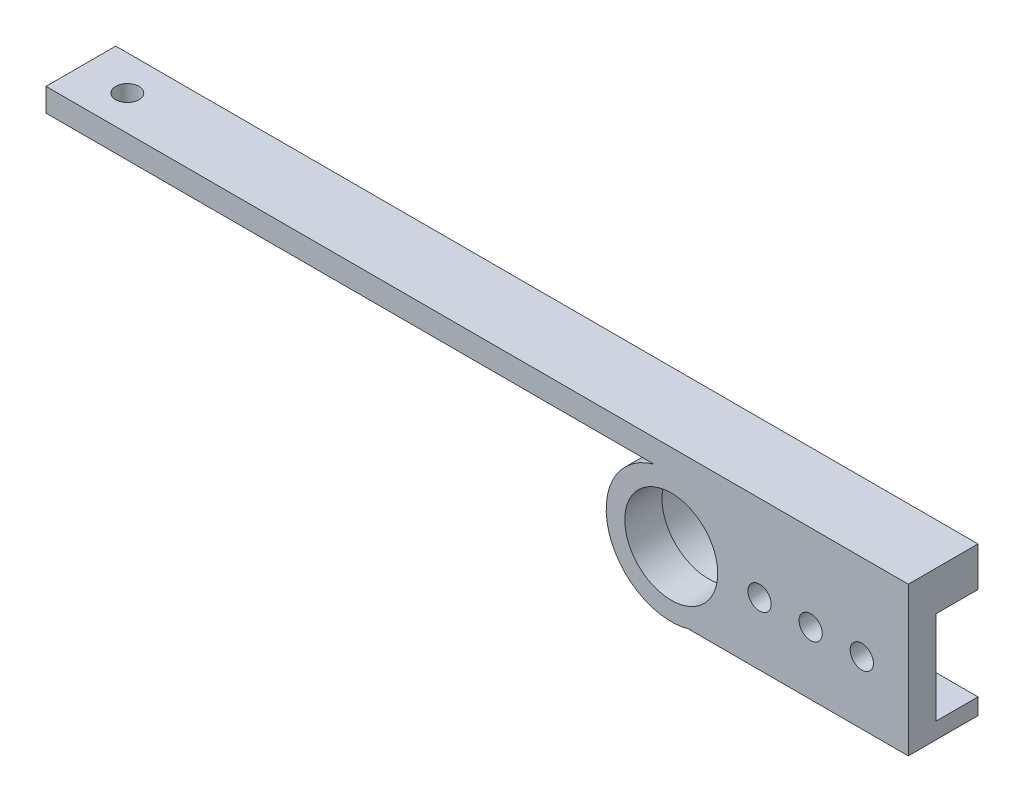
SolidWorks part; units mm, degrees
ref_plane "前视基准面" through (0, 0, 0) normal (0, 0, 1) x (1, 0, 0)
ref_plane "上视基准面" through (0, 0, 0) normal (0, 1, 0) x (1, 0, 0)
ref_plane "右视基准面" through (0, 0, 0) normal (1, 0, 0) x (0, 0, -1)
sketch "草图1" plane through (0, 0, 0) normal (0, 0, 1) x (1, 0, 0)
  line L1 (20, -10) -> (-20, -10)
  line L2 (20, -10) -> (20, 10)
  line L3 (20, 10) -> (-20, 10)
  line L4 (-20, -10) -> (-20, 10)
  line L5 (20, -10) -> (-20, 10) construction
  line L6 (20, 10) -> (-20, -10) construction
  point P0 (0, 0)
  dimension "D1" = 40
  dimension "D2" = 20
extrude "凸台-拉伸1" add sketch "草图1" along normal blind 6
sketch "草图2" plane through (0, 0, 6) normal (0, 0, 1) x (1, 0, 0)
  line L0 (20, -10) -> (20, 10) construction
  circle A0 centre (10, 0) radius 2.5
  circle A1 centre (-1, 0) radius 2.5
  circle A2 centre (-12, 0) radius 2.5
  dimension "D1" = 10
  dimension "D2" = 5
  dimension "D3" = 3
extrude "切除-拉伸1" cut sketch "草图2" against normal through all
sketch "草图3" plane through (0, 0, 6) normal (0, 0, 1) x (1, 0, 0)
  line L0 (20, 13.5) -> (20, 10)
  line L1 (20, -13.5) -> (-26.894, -13.5)
  line L3 (20, 13.5) -> (-26.894, 13.5)
  line L4 (-20, 10) -> (-20, -10)
  line L5 (-20, -10) -> (20, -10)
  line L6 (20, -10) -> (20, 10)
  line L7 (20, 10) -> (-20, 10)
  line L8 (-20, 10) -> (-20, -10)
  line L9 (-20, -10) -> (20, -10)
  line L10 (20, -10) -> (20, 10)
  line L11 (20, 10) -> (-20, 10)
  line L12 (-26.894, -13.5) -> (-26.894, 13.5)
  line L13 (20, -10.0394) -> (-26.894, 13.5) construction
  line L14 (20, 10.0394) -> (-26.894, -13.5) construction
  line L15 (20, -10) -> (20, -13.5)
  circle A0 centre (-31, 0) radius 11
  circle A1 centre (-31, 0) radius 14
  point P2 (0, 0)
  line M10 (-20, 10) -> (-20, -10)
  line M11 (-20, -10) -> (20, -10)
  line M13 (20, 10) -> (-20, 10)
  dimension "D3" = 22
  dimension "D4" = 28
  dimension "D2" = 3.5
  dimension "D1" = 0
extrude "凸台-拉伸2" add sketch "草图3" against normal blind 15 contours L3 A1 L1 L12 A0 | A1 L1 L15 M11 M10 | L1 A1 L8 A0 L12 | L8 A1 L3 L12 A0 | L8 A1 | A1 L0 L3 M10 M13 region at (-1.9449, 11.7771, 6) region at (-1.9449, -11.7771, 6) region at (-23.0173, 9.0328, 6) region at (-27.2274, 11.7946, 6) region at (-18.7882, 0, 6) region at (-23.0173, -9.0328, 6)
sketch "草图5" plane through (0, 0, 6) normal (0, 0, 1) x (1, 0, 0)
  circle A0 centre (-31, 0) radius 10
  circle A1 centre (-31, 0) radius 11 construction
  circle A2 centre (-31, 0) radius 11
  dimension "D1" = 20
extrude "凸台-拉伸3" add sketch "草图5" against normal blind 8
sketch "草图6" plane through (0, 0, 6) normal (0, 0, 1) x (1, 0, 0)
  circle A0 centre (-31, 0) radius 8.5
  circle A1 centre (-31, 0) radius 10 construction
  circle A2 centre (-31, 0) radius 10
  dimension "D1" = 17
sketch "草图7" plane through (0, 13.5, 0) normal (0, 1, 0) x (1, 0, 0)
  circle A0 centre (-17.1666, 1.953) radius 2.6594
sketch "草图8" plane through (20, 0, 0) normal (1, 0, 0) x (0, 0, -1)
  line L1 (-6, 13.5) -> (9, 13.5)
  line L2 (-6, 13.5) -> (-6, 18.5)
  line L3 (-6, 18.5) -> (9, 18.5)
  line L4 (9, 13.5) -> (9, 18.5)
  dimension "D1" = 5
extrude "凸台-拉伸4" add sketch "草图8" against normal blind 500
sketch "草图9" plane through (0, 0, -9) normal (0, 0, -1) x (-1, 0, 0)
  line L1 (24.4567, 15.8334) -> (28.494, 15.8334)
  line L2 (24.4567, 15.8334) -> (24.4567, 12.469)
  line L3 (24.4567, 12.469) -> (28.494, 12.469)
  line L4 (28.494, 15.8334) -> (28.494, 12.469)
extrude "凸台-拉伸5" add sketch "草图9" against normal through all
sketch "草图10" plane through (0, 18.5, 0) normal (0, 1, 0) x (1, 0, 0)
  line L0 (-165.5205, -66.7347) -> (-165.5205, 9)
  line L1 (-165.5205, -66.7347) -> (-49.8553, -66.7347) construction
  line L2 (-165.5205, 229.1717) -> (-165.5205, -140.8283) construction
  line L3 (-480, 9) -> (20, 9) construction
sketch "草图11" plane through (0, 18.5, 0) normal (0, 1, 0) x (1, 0, 0)
  line L1 (-165.5205, -66.7347) -> (-495.6366, -66.7347)
  line L2 (-165.5205, -66.7347) -> (-165.5205, 25.3653)
  line L3 (-165.5205, 25.3653) -> (-495.6366, 25.3653)
  line L4 (-495.6366, -66.7347) -> (-495.6366, 25.3653)
extrude "切除-拉伸2" cut sketch "草图11" against normal through all
sketch "草图12" plane through (0, 18.5, 0) normal (0, 1, 0) x (1, 0, 0)
  line L0 (-165.5205, 9) -> (-165.5205, -6)
  line L1 (-165.5205, 1.5) -> (-155.5205, 1.5) construction
  circle A0 centre (-155.5205, 1.5) radius 2.5
  dimension "D2" = 5
  dimension "D1" = 10
extrude "切除-拉伸3" cut sketch "草图12" against normal blind 10 contours A0 region at (-155.5205, 18.5, -1.5)
